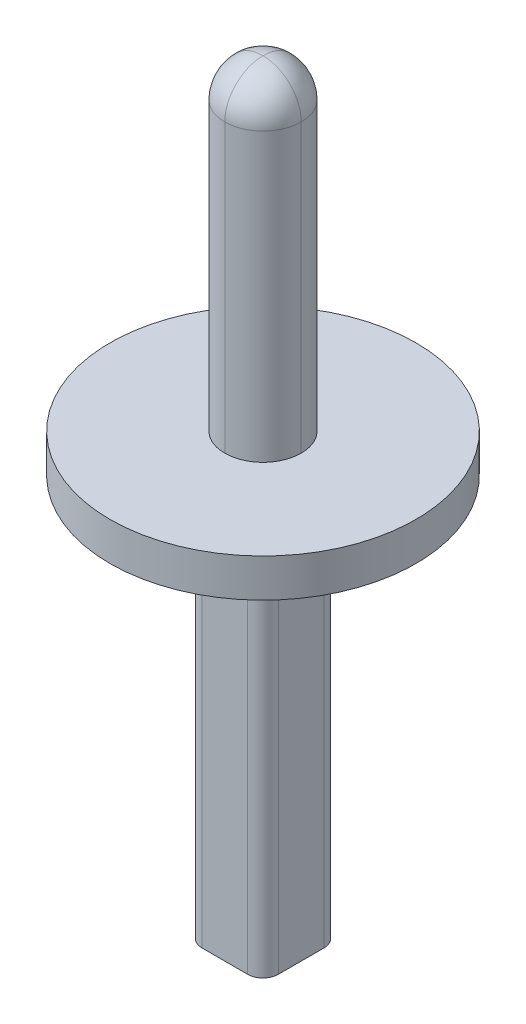
SolidWorks part; units mm, degrees
ref_plane "Front Plane" through (0, 0, 0) normal (0, 0, 1) x (1, 0, 0)
ref_plane "Top Plane" through (0, 0, 0) normal (0, 1, 0) x (1, 0, 0)
ref_plane "Right Plane" through (0, 0, 0) normal (1, 0, 0) x (0, 0, -1)
sketch "Sketch1" plane through (0, 0, 0) normal (0, 1, 0) x (1, 0, 0)
  line L1 (-5, -5) -> (5, -5)
  line L2 (-5, -5) -> (-5, 5)
  line L3 (-5, 5) -> (5, 5)
  line L4 (5, -5) -> (5, 5)
  line L5 (-5, -5) -> (5, 5) construction
  line L6 (-5, 5) -> (5, -5) construction
  point P0 (0, 0)
  dimension "D1" = 10
  dimension "D2" = 10
extrude "Boss-Extrude1" add sketch "Sketch1" along normal mid plane 100
sketch "Sketch2" plane through (0, 50, 0) normal (0, 1, 0) x (1, 0, 0)
  line L1 (-5, 5) -> (5, 5)
  line L2 (-5, 5) -> (-5, -5)
  line L3 (-5, -5) -> (5, -5)
  line L4 (5, 5) -> (5, -5)
  circle A0 centre (0, 0) radius 20
  dimension "D1" = 40
extrude "Boss-Extrude2" add sketch "Sketch2" along normal mid plane 5 from offset 45 offset against normal yes
fillet "Fillet2" radius 2 4 edges at (-5, -23.75, -5) (5, -23.75, -5) (-5, -23.75, 5) (5, -23.75, 5)
fillet "Fillet3" radius 5 4 edges at (-5, 28.75, -5) (-5, 28.75, 5) (5, 28.75, 5) (5, 28.75, -5)
fillet "Fillet4" radius 5 4 edges at (3.5355, 50, 3.5355) (-3.5355, 50, 3.5355) (-3.5355, 50, -3.5355) (3.5355, 50, -3.5355)
